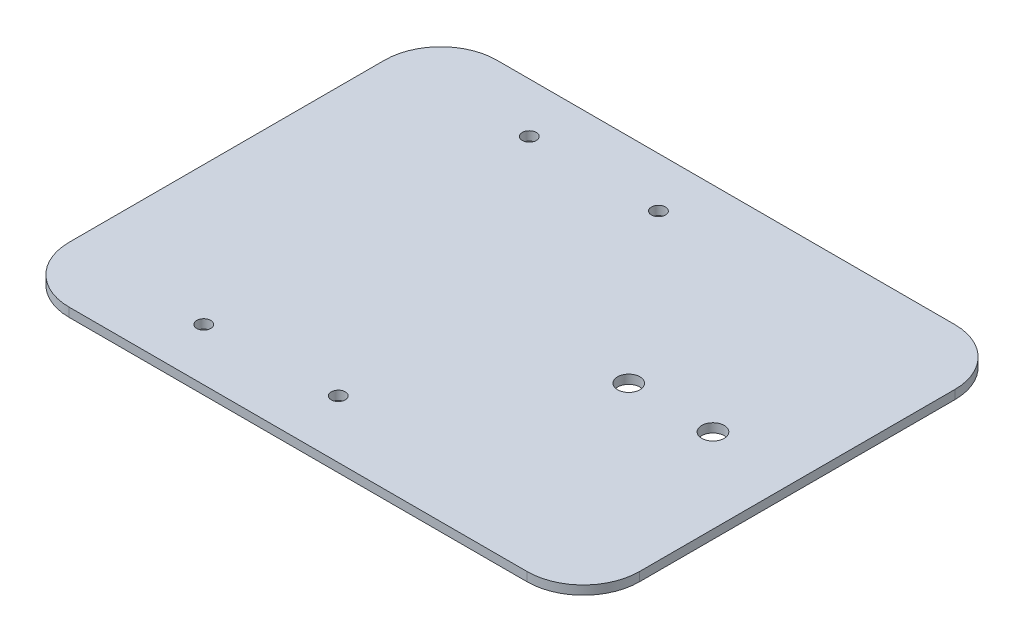
SolidWorks part; units mm, degrees
ref_plane "Front Plane" through (0, 0, 0) normal (0, 0, 1) x (1, 0, 0)
ref_plane "Top Plane" through (0, 0, 0) normal (0, 1, 0) x (1, 0, 0)
ref_plane "Right Plane" through (0, 0, 0) normal (1, 0, 0) x (0, 0, -1)
sketch "Sketch1" plane through (0, 0, 0) normal (0, 1, 0) x (1, 0, 0)
  line L1 (50.8, -38.1) -> (-50.8, -38.1)
  line L2 (50.8, -38.1) -> (50.8, 38.1)
  line L3 (50.8, 38.1) -> (-50.8, 38.1)
  line L4 (-50.8, -38.1) -> (-50.8, 38.1)
  line L5 (50.8, -38.1) -> (-50.8, 38.1) construction
  line L6 (50.8, 38.1) -> (-50.8, -38.1) construction
  point P0 (0, 0)
  dimension "D1" = 101.6
  dimension "D2" = 76.2
extrude "Boss-Extrude1" add sketch "Sketch1" along normal blind 1.5875
sketch "Sketch2" plane through (0, 1.5875, 0) normal (0, 1, 0) x (1, 0, 0)
  line L0 (-14.025, 0) -> (14.025, 0) construction
  line L1 (50.8, -38.1) -> (50.8, 38.1) construction
  circle A0 centre (35.8, 0) radius 2
  circle A1 centre (20.8, 0) radius 2
  dimension "D1" = 4
  dimension "D2" = 4
  dimension "D3" = 15
  dimension "D4" = 15
extrude "Cut-Extrude1" cut sketch "Sketch2" against normal through all
fillet "Fillet1" radius 10 4 edges at (-50.8, 0.7937, -38.1) (-50.8, 0.7937, 38.1) (50.8, 0.7937, 38.1) (50.8, 0.7937, -38.1)
sketch "Sketch4" plane through (0, 1.5875, 0) normal (0, 1, 0) x (1, 0, 0)
  circle A0 centre (-3.1344, 29.2185) radius 1.25
  circle A1 centre (-3.1344, -27.8181) radius 1.25
  circle A2 centre (-26.1344, 29.2185) radius 1.25
  circle A3 centre (-26.1344, -28.7815) radius 1.25
  dimension "D1" = 2.5
  dimension "D2" = 2.5
  dimension "D3" = 2.5
  dimension "D4" = 2.5
  dimension "D5" = 23
  dimension "D6" = 23
  dimension "D7" = 58
extrude "Cut-Extrude2" cut sketch "Sketch4" against normal through all
